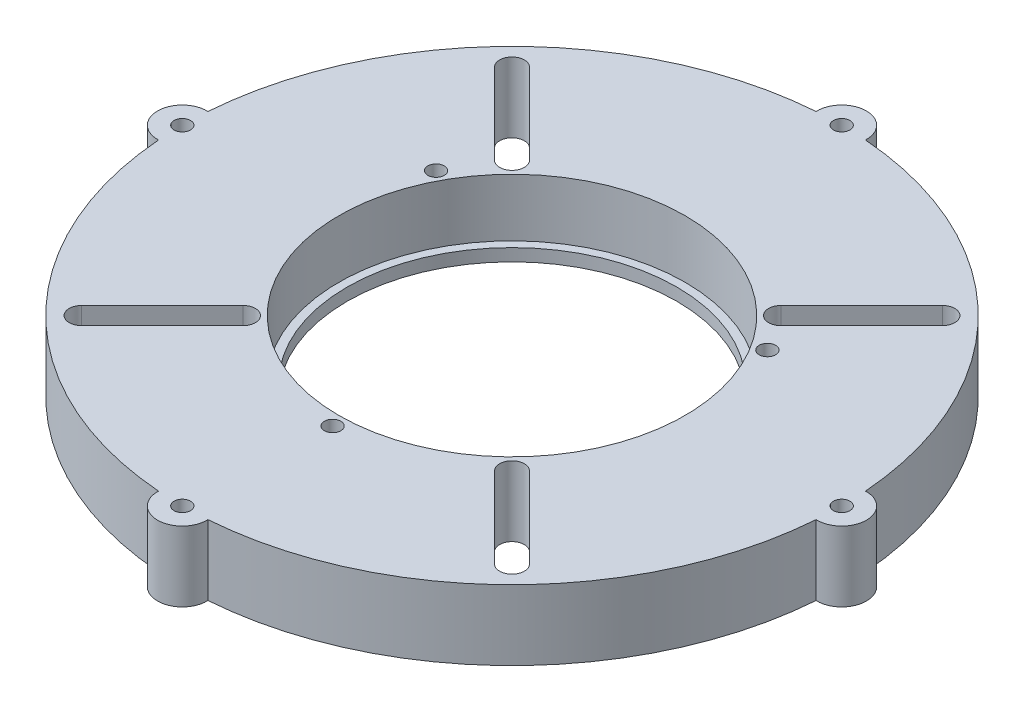
SolidWorks part; units mm, degrees
material "Aluminum 7075-T6 (2)"
ref_plane "Front Plane" through (0, 0, 0) normal (0, 0, 1) x (1, 0, 0)
ref_plane "Top Plane" through (0, 0, 0) normal (0, 1, 0) x (1, 0, 0)
ref_plane "Right Plane" through (0, 0, 0) normal (1, 0, 0) x (0, 0, -1)
sketch "Sketch1" plane through (0, 0, 0) normal (0, 1, 0) x (1, 0, 0)
  circle A0 centre (0, 0) radius 20
  circle A1 centre (0, 0) radius 40
extrude "Boss-Extrude1" add sketch "Sketch1" along normal blind 8.5 contours A1 | A0
sketch "Sketch2" plane through (0, 8.5, 0) normal (0, 1, 0) x (1, 0, 0)
  circle A0 centre (40, 0) radius 3
  circle A1 centre (40, 0) radius 1
extrude "Cut-Extrude2" cut sketch "Sketch2" against normal through all contours A1
extrude "Boss-Extrude3" add sketch "Sketch2<6>" against normal blind 8.5
sketch "Sketch2<6>" plane through (0, 8.5, 0) normal (0, 1, 0) x (1, 0, 0) same geometry as "Sketch2"
pattern_circular "CirPattern1" count 4 over 360 about axis through (0, 8.5, 0) along (0, 1, 0) of "Cut-Extrude2", "Boss-Extrude3"
sketch "Sketch4" plane through (0, 8.5, 0) normal (0, 1, 0) x (1, 0, 0)
  line L0 (-26.1099, -26.1099) -> (-16.3165, -16.3165) construction
  line L1 (-27.1706, -25.0493) -> (-17.3771, -15.2558)
  line L2 (-25.0493, -27.1706) -> (-15.2558, -17.3771)
  line L3 (-21.2132, -21.2132) -> (0, 0) construction
  arc A0 (-27.1706, -25.0493) -> (-25.0493, -27.1706) centre (-26.1099, -26.1099) ccw
  arc A1 (-15.2558, -17.3771) -> (-17.3771, -15.2558) centre (-16.3165, -16.3165) ccw
  circle A2 centre (0, 0) radius 20 construction
  point P2 (-21.2132, -21.2132)
  dimension "D1" = 13.85
  dimension "D2" = 1.5
  dimension "D3" = 23.075
extrude "Cut-Extrude4" cut sketch "Sketch4" against normal through all
pattern_circular "CirPattern3" count 4 over 360 about axis through (0, 8.5, 0) along (0, 1, 0) of "Cut-Extrude4"
sketch "Sketch7" plane through (0, 8.5, 0) normal (0, 1, 0) x (1, 0, 0)
  circle A0 centre (0, 0) radius 21
extrude "Cut-Extrude5" cut sketch "Sketch7" against normal blind 7
sketch "Sketch8" plane through (0, 8.5, 0) normal (0, 1, 0) x (1, 0, 0)
  circle A0 centre (0.7201, -22.4885) radius 1
  circle A1 centre (19.1156, 11.8678) radius 1
  circle A2 centre (-19.8356, 10.6207) radius 1
extrude "Outer_Retainer_M2_Tapped_Envelope" cut sketch "Sketch8" against normal blind 4.3
